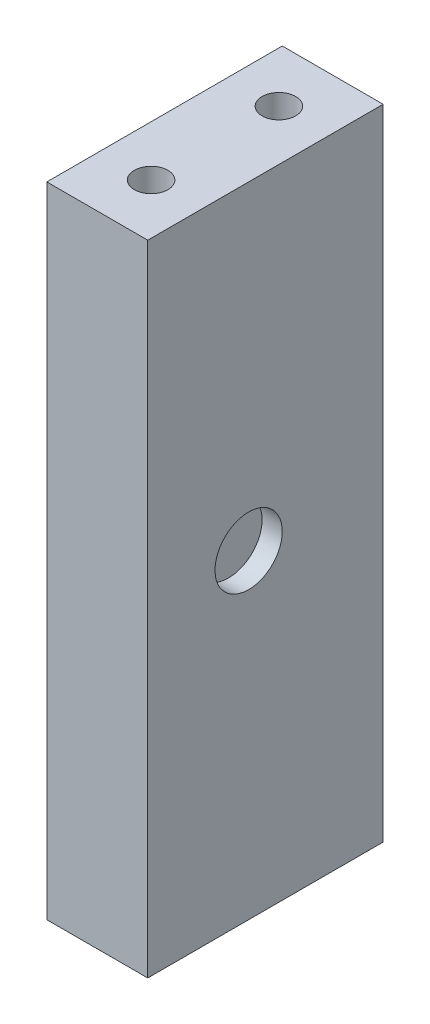
SolidWorks part; units mm, degrees
material "ABS"
ref_plane "Front Plane" through (0, 0, 0) normal (0, 0, 1) x (1, 0, 0)
ref_plane "Top Plane" through (0, 0, 0) normal (0, 1, 0) x (1, 0, 0)
ref_plane "Right Plane" through (0, 0, 0) normal (1, 0, 0) x (0, 0, -1)
sketch "Sketch1" plane through (0, 0, 0) normal (0, 1, 0) x (1, 0, 0)
  line L0 (0, 0) -> (7.5, 0) construction
  line L1 (7.5, -17.5) -> (-7.5, -17.5)
  line L2 (7.5, -17.5) -> (7.5, 17.5)
  line L3 (7.5, 17.5) -> (-7.5, 17.5)
  line L4 (-7.5, -17.5) -> (-7.5, 17.5)
  line L5 (7.5, -17.5) -> (-7.5, 17.5) construction
  line L6 (7.5, 17.5) -> (-7.5, -17.5) construction
  circle A0 centre (0, 9.5) radius 2.5
  circle A1 centre (0, -9.5) radius 2.5
  point P0 (0, 0)
  point P12 (0, 0)
  dimension "D4" = 5
  dimension "D1" = 15
  dimension "D2" = 35
  dimension "D3" = 8
extrude "Boss-Extrude1" add sketch "Sketch1" along normal mid plane 95
sketch "Sketch2" plane through (7.5, 0, 0) normal (1, 0, 0) x (0, 0, -1)
  line L1 (17.5, 47.5) -> (17.5, -47.5) construction
  circle A0 centre (-2.5, 0) radius 5
  dimension "D1" = 10
  dimension "D2" = 20
extrude "Cut-Extrude1" cut sketch "Sketch2" against normal blind 3
